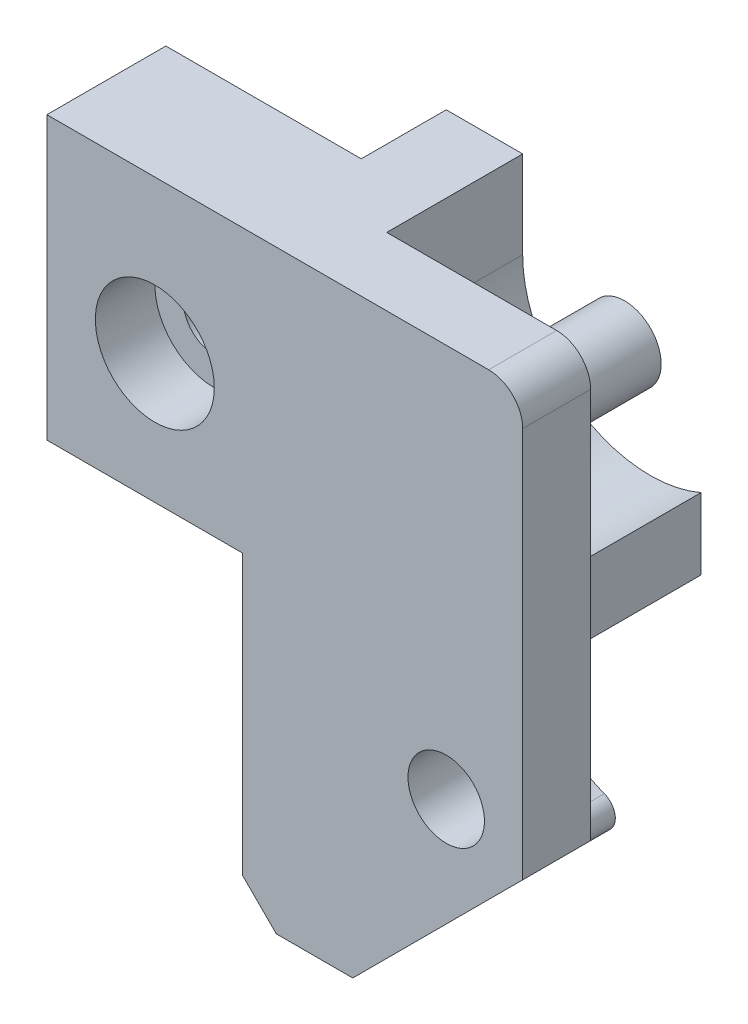
SolidWorks part; units mm, degrees
note: The reader was unsure of these and kept them because the rebuilt part matched: shared geometry of "Sketch2<3>", "Sketch2<5>".
material "ABS"
ref_plane "Front Plane" through (0, 0, 0) normal (0, 0, 1) x (1, 0, 0)
ref_plane "Top Plane" through (0, 0, 0) normal (0, 1, 0) x (1, 0, 0)
ref_plane "Right Plane" through (0, 0, 0) normal (1, 0, 0) x (0, 0, -1)
sketch "Sketch1" plane through (0, 0, 0) normal (0, 0, 1) x (1, 0, 0)
  line L0 (18, 0) -> (28, 10)
  line L1 (0, 0) -> (18, 0)
  line L2 (0, 0) -> (0, 35)
  line L3 (0, 35) -> (26, 35)
  line L4 (28, 10) -> (28, 33)
  arc A0 (28, 33) -> (26, 35) centre (26, 33) ccw
  point P3 (28, 0)
  dimension "D1" = 2
  dimension "D2" = 35
  dimension "D3" = 28
extrude "Boss-Extrude1" add sketch "Sketch1" along normal blind 4
sketch "Sketch2" plane through (0, 0, 0) normal (0, 0, -1) x (-1, 0, 0)
  line L0 (-23.5, 11.864) -> (-23.5, 29.864) construction
  line L1 (-28, 10) -> (-28, 33) construction
  line L2 (-18, 0) -> (-28, 10) construction
  line L3 (-21.1583, 3.1583) -> (-18, 0)
  line L4 (-26.5, 22.9901) -> (-26.5, 18.7923)
  line L5 (-15.95, 18.414) -> (-23.5, 18.414)
  line L6 (-15.95, 18.414) -> (-15.95, 5.314)
  line L7 (-15.95, 5.314) -> (-23.5, 5.314)
  line L8 (-23.5, 18.414) -> (-23.5, 5.314)
  line L9 (-16, 29.864) -> (-16, 35)
  line L10 (-26, 35) -> (0, 35) construction
  line L11 (-16, 35) -> (-18.0346, 35)
  circle A0 centre (-23.5, 29.864) radius 2.15
  circle A1 centre (-23.5, 11.864) radius 2.25
  circle A2 centre (-23.5, 11.864) radius 7.55
  circle A3 centre (-23.5, 29.864) radius 7.5
  arc A4 (-19.725, 5.314) -> (-20.8073, 4.7998) centre (-23.5, 11.864) cw
  arc A5 (-21.1583, 3.1583) -> (-20.8073, 4.7998) centre (-20.4511, 3.8654) cw
  dimension "D1" = 4.3
  dimension "D2" = 4.5
  dimension "D5" = 15.1
  dimension "D3" = 15
  dimension "D8" = 1
  dimension "D4" = 18
  dimension "D6" = 13.1
  dimension "D7" = 1.5
extrude "Cut-Extrude1" cut sketch "Sketch2" against normal through all contours A1
extrude "Boss-Extrude2" add sketch "Sketch2<3>" along normal blind 8 contours A0
sketch "Sketch2<3>" plane through (0, 0, 0) normal (0, 0, -1) x (-1, 0, 0) same geometry as "Sketch2"
extrude "Boss-Extrude4" add sketch "Sketch2<5>" along normal up to surface (8 mm away)
sketch "Sketch2<5>" plane through (0, 0, 0) normal (0, 0, -1) x (-1, 0, 0) same geometry as "Sketch2"
sketch "Sketch6" plane through (0, 0, -8) normal (0, 0, -1) x (-1, 0, 0)
  line L0 (-15.95, 18.414) -> (-19.745, 18.414) construction
  line L1 (0, 0) -> (-11.5, 0)
  line L2 (0, 0) -> (0, 18.414)
  line L3 (0, 18.414) -> (-11.5, 18.414)
  line L4 (-11.5, 0) -> (-11.5, 18.414)
  dimension "D1" = 11.5
extrude "Cut-Extrude2" cut sketch "Sketch6" against normal through all
sketch "Sketch12" plane through (15.95, 0, 0) normal (1, 0, 0) x (0, 0, -1)
  line L4 (0, 18.414) -> (0, 5.314)
  line L5 (0, 5.314) -> (8, 5.314)
  line L6 (8, 5.314) -> (8, 18.414)
  line L7 (8, 18.414) -> (0, 18.414)
  line L8 (0, 18.414) -> (0, 5.314)
  line L9 (0, 5.314) -> (8, 5.314)
  line L10 (8, 5.314) -> (8, 18.414)
  line L11 (8, 18.414) -> (0, 18.414)
  dimension "D1" = 0
extrude "Cut-Extrude3" cut sketch "Sketch12" against normal through all
sketch "Sketch3" plane through (0, 0, 4) normal (0, 0, 1) x (1, 0, 0)
  line L5 (0, 18.414) -> (19.745, 18.414)
  line L6 (0, 35) -> (0, 18.414)
  line L7 (16, 35) -> (0, 35)
  line L8 (16, 29.864) -> (16, 35)
  line L9 (26.5, 18.7923) -> (26.5, 22.9901)
  line L10 (0, 18.414) -> (19.745, 18.414)
  line L11 (0, 35) -> (0, 18.414)
  line L12 (16, 35) -> (0, 35)
  line L13 (16, 29.864) -> (16, 35)
  line L14 (26.5, 18.7923) -> (26.5, 22.9901)
  circle A0 centre (6.35, 26) radius 3.5
  arc A3 (16, 29.864) -> (26.5, 22.9901) centre (23.5, 29.864) ccw
  arc A4 (26.5, 18.7923) -> (19.745, 18.414) centre (23.5, 11.864) ccw
  arc A5 (16, 29.864) -> (26.5, 22.9901) centre (23.5, 29.864) ccw
  arc A6 (26.5, 18.7923) -> (19.745, 18.414) centre (23.5, 11.864) ccw
  dimension "D2" = 7
  dimension "D3" = 6.35
  dimension "D4" = 9
  dimension "D1" = 0
hole_wizard "CBORE for #6 Socket Head Cap Screw1" positions "Sketch5" profile "Sketch4" counterbore size "#6" standard "ANSI Inch" end condition through all
sketch "Sketch5" plane through (0, 0, 4) normal (0, 0, 1) x (1, 0, 0)
  point P0 (6.35, 26)
sketch "Sketch4" plane through (6.35, 26, 4) normal (1, 0, 0) x (0, -1, 0)
  line L0 (0, 0) -> (0, 12)
  line L1 (0, 12) -> (1.8288, 12)
  line L3 (1.8288, 12) -> (1.8288, 3.5052)
  line L4 (1.8288, 3.5052) -> (3.5, 3.5052)
  line L5 (3.5, 3.5052) -> (3.5, 0)
  line L7 (3.5, 0) -> (0, 0)
  line L11 (0, -6.35) -> (0, 107.95) construction
  dimension "Thru Hole Dia." = 3.6576
  dimension "Thru Hole Depth" = 12
  dimension "C'Bore Dia." = 7
  dimension "C'Bore Depth" = 3.5052
sketch "Sketch13" plane through (0, 0, -8) normal (0, 0, -1) x (-1, 0, 0)
  line L1 (0, 18.414) -> (-11.5, 18.414)
  line L2 (0, 18.414) -> (0, 35)
  line L3 (0, 35) -> (-11.5, 35)
  line L4 (-11.5, 18.414) -> (-11.5, 35)
  line L5 (0, 35) -> (-16, 35) construction
  line L7 (-11.5, 5.314) -> (-11.5, 0)
extrude "Cut-Extrude4" cut sketch "Sketch13" against normal blind 5
chamfer "Chamfer1" distance 2 angle 45 1 edges at (11.5, 0, -2)
sketch "Sketch14" plane through (0, 0, -8) normal (0, 0, -1) x (-1, 0, 0)
  circle A0 centre (-23.5, 29.864) radius 2.15
extrude "Cut-Extrude5" cut sketch "Sketch14" against normal blind 1.5
